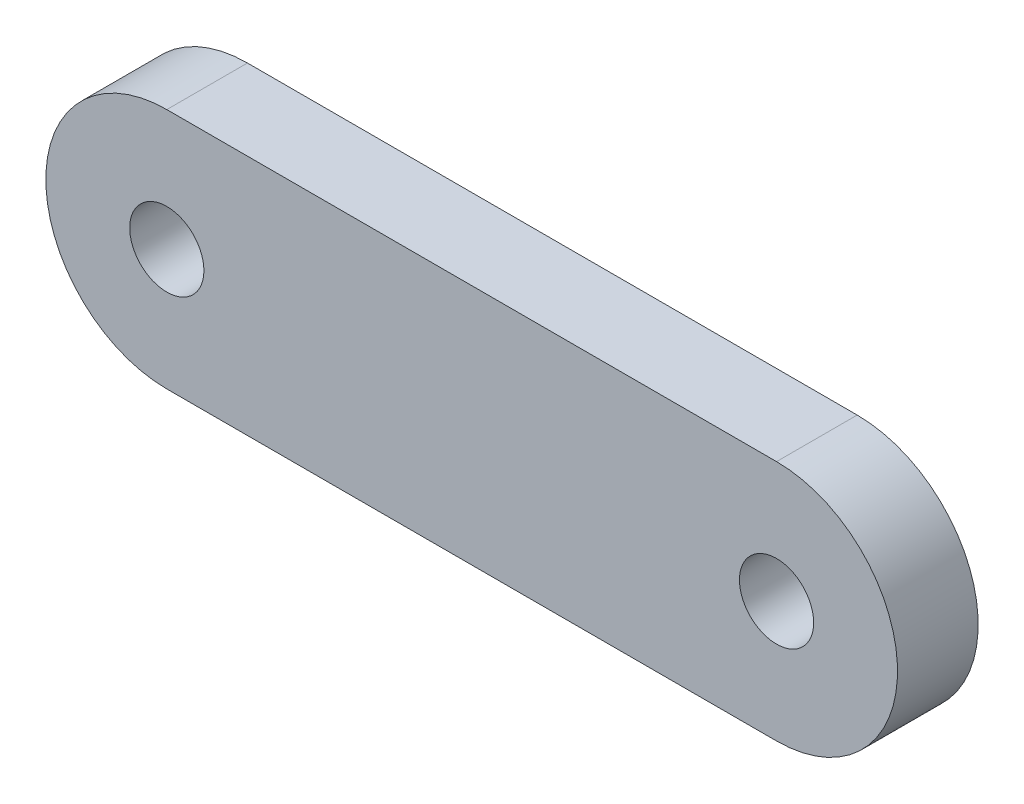
SolidWorks part; units mm, degrees
ref_plane "前视基准面" through (0, 0, 0) normal (0, 0, 1) x (1, 0, 0)
ref_plane "上视基准面" through (0, 0, 0) normal (0, 1, 0) x (1, 0, 0)
ref_plane "右视基准面" through (0, 0, 0) normal (1, 0, 0) x (0, 0, -1)
other "Configuration Table"
sketch "草图1" plane through (0, 0, 0) normal (0, 0, 1) x (1, 0, 0)
  line L1 (-18.9, 7.5) -> (18.9, 7.5)
  line L3 (-18.9, -7.5) -> (18.9, -7.5)
  line L5 (-18.9, 7.5) -> (18.9, -7.5) construction
  line L6 (-18.9, -7.5) -> (18.9, 7.5) construction
  arc A0 (-18.9, 7.5) -> (-18.9, -7.5) centre (-18.9, 0) ccw
  arc A1 (18.9, 7.5) -> (18.9, -7.5) centre (18.9, 0) cw
  circle A2 centre (-18.9, 0) radius 2.3
  circle A3 centre (18.9, 0) radius 2.3
  point P0 (0, 0)
  dimension "D1" = 4.6
  dimension "D2" = 4.6
  dimension "D4" = 15
  dimension "D3" = 37.8
extrude "凸台-拉伸1" add sketch "草图1" along normal blind 5
equation "\"fi\"=4.6"
equation "\"D1@草图1\"=\"fi\""
equation "\"D2@草图1\"=\"fi\""
equation "\"b0\"= 75.6'ground"
equation "\"width\"=15"
equation "\"D4@草图1\"=\"width\""
equation "\"depth\"=5"
equation "\"D1@凸台-拉伸1\"=\"depth\""
equation "\"b1\"= \"b0\" *1.4/ 2'rocker"
equation "\"b2\"= \"b0\"'coupler"
equation "\"b3\"= \"b0\" / 2'coupler"
equation "\"b4\"= \"b0\" *2'leg"
equation "\"angle\"= 90度'左右cranker夹角"
equation "\"D3@草图1\"=\"b3\""
